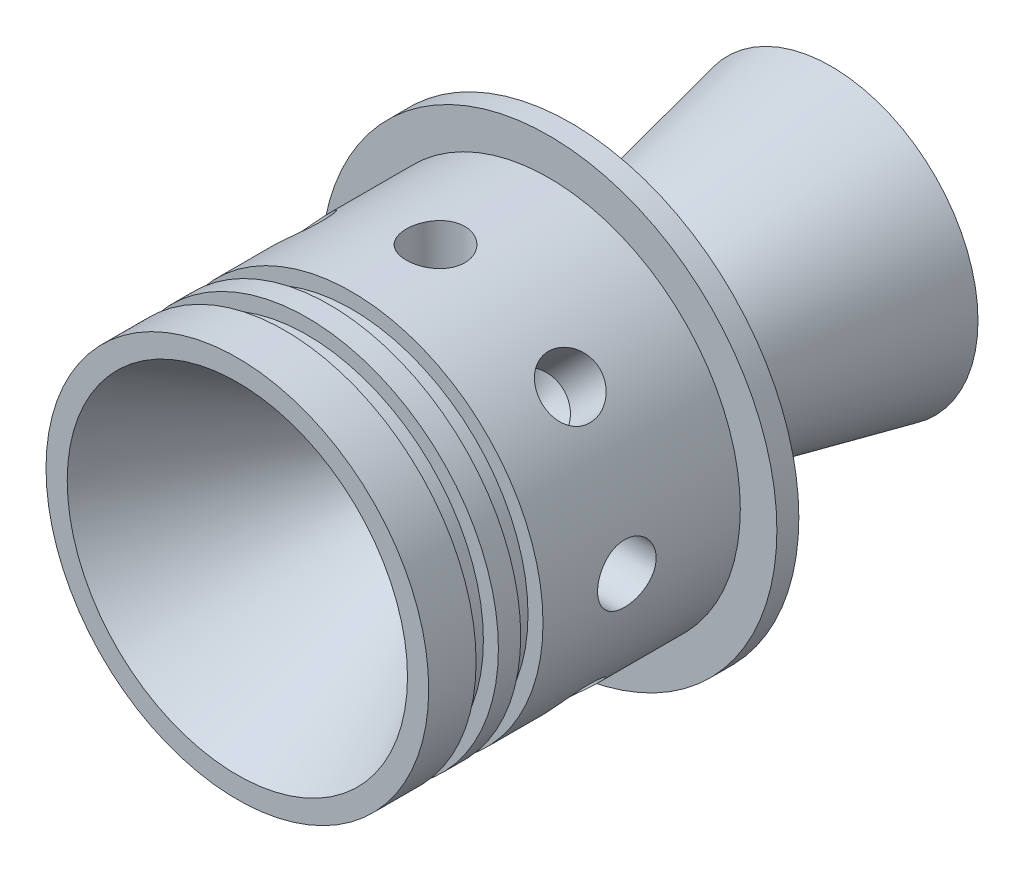
SolidWorks part; units mm, degrees
material "AISI 1045 Steel, cold drawn"
ref_plane "Alzado" through (0, 0, 0) normal (0, 0, 1) x (1, 0, 0)
ref_plane "Planta" through (0, 0, 0) normal (0, 1, 0) x (1, 0, 0)
ref_plane "Vista lateral" through (0, 0, 0) normal (1, 0, 0) x (0, 0, -1)
sketch "Croquis2" plane through (0, 0, 0) normal (1, 0, 0) x (0, 0, -1)
  line L0 (-14.0172, 0) -> (56.1534, 0) construction
  line L1 (0, 23.2509) -> (28.5804, 6.75)
  line L3 (0, 23.2509) -> (0, 26.1493)
  line L4 (0, 26.1493) -> (6.476, 26.1493)
  line L5 (45.5804, 26.0993) -> (45.5804, 12.4942)
  line L7 (81.1552, 20.0559) -> (81.1552, 17.5)
  line L8 (6.476, 26.1493) -> (6.476, 24.0993)
  line L9 (6.476, 24.0993) -> (9.524, 24.0993)
  line L10 (9.524, 24.0993) -> (9.524, 26.1493)
  line L11 (9.524, 26.1493) -> (12.572, 26.1493)
  line L13 (30.5804, 6.75) -> (81.1552, 17.5)
  line L15 (45.5804, 12.4942) -> (81.1552, 20.0559)
  line L16 (28.5804, 6.75) -> (30.5804, 6.75)
  line L18 (16.3437, 13.8149) -> (19.3157, 12.099) construction
  line L19 (19.0363, 6.8) -> (17.4124, 6.8) construction
  line L20 (19.4766, 6.8) -> (20.8834, 6.8) construction
  line L21 (30.5804, 8.6394) -> (30.5804, -5.1694) construction
  line L22 (12.572, 26.1493) -> (12.572, 24.0993)
  line L23 (12.572, 24.0993) -> (15.62, 24.0993)
  line L24 (15.62, 24.0993) -> (15.62, 26.1493)
  line L25 (15.62, 26.1493) -> (42.5804, 26.1493)
  line L26 (45.5804, 26.0993) -> (45.5804, 31.1493)
  line L27 (45.5804, 31.1493) -> (42.5804, 31.1493)
  line L28 (42.5804, 31.1493) -> (42.5804, 26.1493)
  point P14 (8, 24.0993)
  point P15 (27.0804, 26.1493)
  dimension "D2" = 30
  dimension "D4" = 46.5018
  dimension "D5" = 35
  dimension "D7" = 52.2986
  dimension "D8" = 8
  dimension "D11" = 18.5
  dimension "D13" = 12
  dimension "D9" = 2.05
  dimension "D10" = 3.048
  dimension "D3" = 13.5
  dimension "D6" = 2
  dimension "D14" = 40.1117
  dimension "D12" = 2.5
  dimension "D15" = 15
  dimension "D16" = 3
  dimension "D17" = 5
revolve "Revolución1" add sketch "Croquis2" angle 360 about L0
ref_plane "Plano1" through (0, 26.1493, 0) normal (0, 1, 0) x (1, 0, 0)
sketch "Croquis3" plane through (0, 26.1493, 0) normal (0, 1, 0) x (1, 0, 0)
  line L0 (26.1493, 45.5804) -> (-26.1493, 45.5804) construction
  point P0 (0, 27.0804)
  dimension "D1" = 18.5
hole_wizard "Ø8.0mm Dowel Hole1" positions "Croquis3" profile "Croquis5" hole size "Ø8.0" standard "ANSI Metric"
sketch "Croquis5" plane through (0, 26.1493, -27.0804) normal (1, 0, 0) x (0, 0, 1)
  line L0 (0, 0) -> (0, 9.4034)
  line L1 (0, 9.4034) -> (4, 7)
  line L2 (4, 7) -> (4, 0)
  line L5 (4, 0) -> (0, 0)
  line L10 (0, 9.4034) -> (-4, 7) construction
  line L11 (0, -6.35) -> (0, 107.95) construction
  dimension "Diámetro de taladro" = 8
  dimension "Profundidad de taladro" = 7
  dimension "Ángulo de perforador" = 118
pattern_circular "MatrizC1" count 8 over 360 about axis through (0, 0, -15.62) along (0, 0, 1) of "Ø8.0mm Dowel Hole1"
equation "\"Dexit\"=35"
equation "\"D5@Croquis2\"=\"Dexit\""
equation "\"IDCase\"= 52.5018"
equation "\"D7@Croquis2\"=\"IDCaseReal\""
equation "\"RadialClearance\"= 0.004in"
equation "\"IDCaseReal\"= \"IDCase\" - \"RadialClearance\" * 2"
equation "\"OringXlocation\"=8"
equation "\"D8@Croquis2\"=\"OringXlocation\""
equation "\"G\"= 3.05mm'O-ring widht gland 0.12<G<0.125 in"
equation "\"D\"= 2.03mm'O-ring depth gland 0.08<D<0.084 in"
equation "\"ScrewXlocation\"= 15 + 3.5'Location plus radius screw M7"
equation "\"D11@Croquis2\"=\"ScrewXlocation\""
equation "\"NozzleBellThickness\"=2.5"
equation "\"D1@Croquis3\"=\"ScrewXlocation\""
equation "\"DnozzleThroat\"=13.5"
equation "\"LengthNozzleThroat\"=2"
equation "\"OuterNozzleBellThickness\"=2"
equation "\"DivergenceAngle\"=12"
equation "\"D13@Croquis2\"=\"DivergenceAngle\""
equation "\"ConvergenceAngle\"=30"
equation "\"D2@Croquis2\"=\"ConvergenceAngle\""
equation "\"ConvergenceThroatRadius\"= 3"
equation "\"DivergenceThroatRadius\"=5"
equation "\"Dchamber\"= \"IDCase\" - 2 * \"AblativeThickness\""
equation "\"D4@Croquis2\"=\"Dchamber\""
equation "\"AblativeThickness\"= 3mm"
equation "\"D3@Croquis2\"=\"DnozzleThroat\""
equation "\"D6@Croquis2\"=\"LengthNozzleThroat\""
equation "\"D12@Croquis2\"=\"NozzleBellThickness\""
